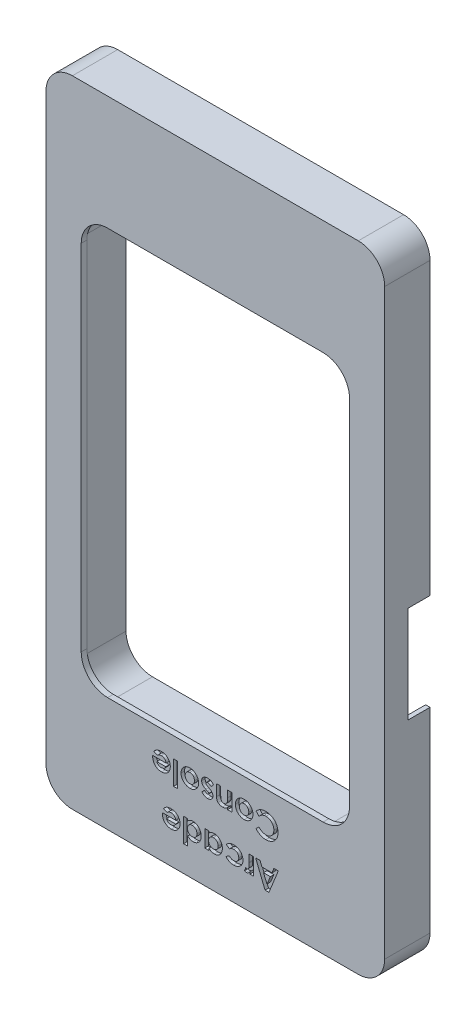
SolidWorks part; units mm, degrees
ref_plane "Ebene vorne" through (0, 0, 0) normal (1, 0, 0) x (0, 1, 0)
ref_plane "Ebene oben" through (0, 0, 0) normal (0, 0, 1) x (0, 1, 0)
ref_plane "Ebene rechts" through (0, 0, 0) normal (0, 1, 0) x (-1, 0, 0)
sketch "DiplayCase" plane through (0, 0, 0) normal (0, 0, 1) x (0, 1, 0)
  line L1 (-46.22, -30.5) -> (46.22, -30.5)
  line L2 (-46.22, -30.5) -> (-46.22, 30.5)
  line L3 (-46.22, 30.5) -> (46.22, 30.5)
  line L4 (46.22, -30.5) -> (46.22, 30.5)
  line L5 (-46.22, -30.5) -> (46.22, 30.5) construction
  line L6 (-46.22, 30.5) -> (46.22, -30.5) construction
  line L7 (-72.22, -38.5) -> (72.22, -38.5)
  line L8 (-72.22, -38.5) -> (-72.22, 38.5)
  line L9 (-72.22, 38.5) -> (72.22, 38.5)
  line L10 (72.22, -38.5) -> (72.22, 38.5)
  line L11 (-72.22, -38.5) -> (72.22, 38.5) construction
  line L12 (-72.22, 38.5) -> (72.22, -38.5) construction
  point P0 (0, 0)
  point P6 (0, 0)
  dimension "D1" = 61
  dimension "D2" = 92.44
  dimension "D3" = 8
  dimension "D4" = 26
extrude "UpperCase" add sketch "DiplayCase" along normal blind 10.3
fillet "Verrundung1" radius 6 4 edges at (30.5, 46.22, 5.15) (-30.5, 46.22, 5.15) (30.5, -46.22, 5.15) (-30.5, -46.22, 5.15)
sketch "Skizze2" plane through (0, 0, 0) normal (0, 0, -1) x (1, 0, 0)
  line L1 (-30.6, -47.32) -> (30.6, -47.32)
  line L2 (-30.6, -47.32) -> (-30.6, 47.32)
  line L3 (-30.6, 47.32) -> (30.6, 47.32)
  line L4 (30.6, -47.32) -> (30.6, 47.32)
  line L5 (-30.6, -47.32) -> (30.6, 47.32) construction
  line L6 (-30.6, 47.32) -> (30.6, -47.32) construction
  point P0 (0, 0)
  dimension "D1" = 61.2
  dimension "D2" = 94.64
extrude "Schnitt-Linear austragen1" cut sketch "Skizze2" against normal blind 9
fillet "Verrundung2" radius 6 4 edges at (38.5, -72.22, 5.15) (-38.5, -72.22, 5.15) (38.5, 72.22, 5.15) (-38.5, 72.22, 5.15)
fillet "Verrundung3" radius 6 4 edges at (-30.6, 47.32, 4.5) (30.6, 47.32, 4.5) (30.6, -47.32, 4.5) (-30.6, -47.32, 4.5)
shell "Wandung2" thickness 1 removed face at (0, 0, 0)
sketch "Skizze8" plane through (0, 0, 10.3) normal (0, 0, 1) x (0, -1, 0)
  line L0 (46.22, 0) -> (72.22, 0) construction
  line L1 (46.22, -24.5) -> (46.22, 24.5) construction
  line L2 (72.22, -32.5) -> (72.22, 32.5) construction
  line L3 (60.9348, 18.5) -> (60.9348, -18.5) construction
  text T0 "Arcade \r\nConsole" font "Century Gothic" height in points 20
  point P9 (0, 0)
  point P10 (60.9348, 0)
extrude "Text_ArcadeConsole" cut sketch "Skizze8" against normal blind 0.8
sketch "Skizze11" plane through (0, 47.32, 0) normal (0, -1, 0) x (1, 0, 0)
  line L1 (-10.85, -4.17) -> (10.85, -4.17)
  line L2 (-10.85, -4.17) -> (-10.85, 4.17)
  line L3 (-10.85, 4.17) -> (10.85, 4.17)
  line L4 (10.85, -4.17) -> (10.85, 4.17)
  line L5 (-10.85, -4.17) -> (10.85, 4.17) construction
  line L6 (-10.85, 4.17) -> (10.85, -4.17) construction
  point P0 (0, 0)
  dimension "D1" = 21.7
  dimension "D2" = 8.34
extrude "Hole_DisplayCables" cut sketch "Skizze11" against normal blind 1
sketch "Skizze12" plane through (0, 0, 9.3) normal (0, 0, -1) x (1, 0, 0)
  line L1 (-31.5, -66) -> (31.5, -66) construction
  line L2 (-31.5, -66) -> (-31.5, 66) construction
  line L3 (-31.5, 66) -> (31.5, 66) construction
  line L4 (31.5, -66) -> (31.5, 66) construction
  line L5 (-31.5, -66) -> (31.5, 66) construction
  line L6 (-31.5, 66) -> (31.5, -66) construction
  circle A2 centre (34, 68) radius 2.5
  circle A3 centre (34, 68) radius 1.25
  circle A4 centre (-34, 68) radius 2.5
  circle A5 centre (-34, 68) radius 1.25
  circle A6 centre (34, -68) radius 2.5
  circle A7 centre (34, -68) radius 1.25
  circle A8 centre (-34, -68) radius 2.5
  circle A9 centre (-34, -68) radius 1.25
  point P0 (0, 0)
  dimension "D3" = 5
  dimension "D4" = 2.5
  dimension "D6" = 2.5
  dimension "D7" = 5
  dimension "D8" = 2.5
  dimension "D11" = 5
  dimension "D12" = 2.5
  dimension "D15" = 5
  dimension "D16" = 2.5
  dimension "D1" = 63
  dimension "D2" = 132
  dimension "D5" = 2
  dimension "D9" = 2.5
  dimension "D10" = 2
  dimension "D13" = 2.5
  dimension "D14" = 2
extrude "Aufsatz-Linear austragen4" add sketch "Skizze12" along normal blind 4 contours A6 | A7 | A4 | A5 | A3 | A2 | A8 | A9
sketch "Skizze16" plane through (38.5, 0, 0) normal (1, 0, 0) x (0, 1, 0)
  line L0 (-66.22, 0) -> (66.22, 0) construction
  line L2 (0.22, 0) -> (-21.78, 0)
  line L3 (0.22, 0) -> (0.22, 5)
  line L4 (0.22, 5) -> (-21.78, 5)
  line L5 (-21.78, 0) -> (-21.78, 5)
  dimension "D1" = 66
  dimension "D2" = 22
  dimension "D3" = 5
extrude "Schnitt-Linear austragen3" cut sketch "Skizze16" against normal blind 11
